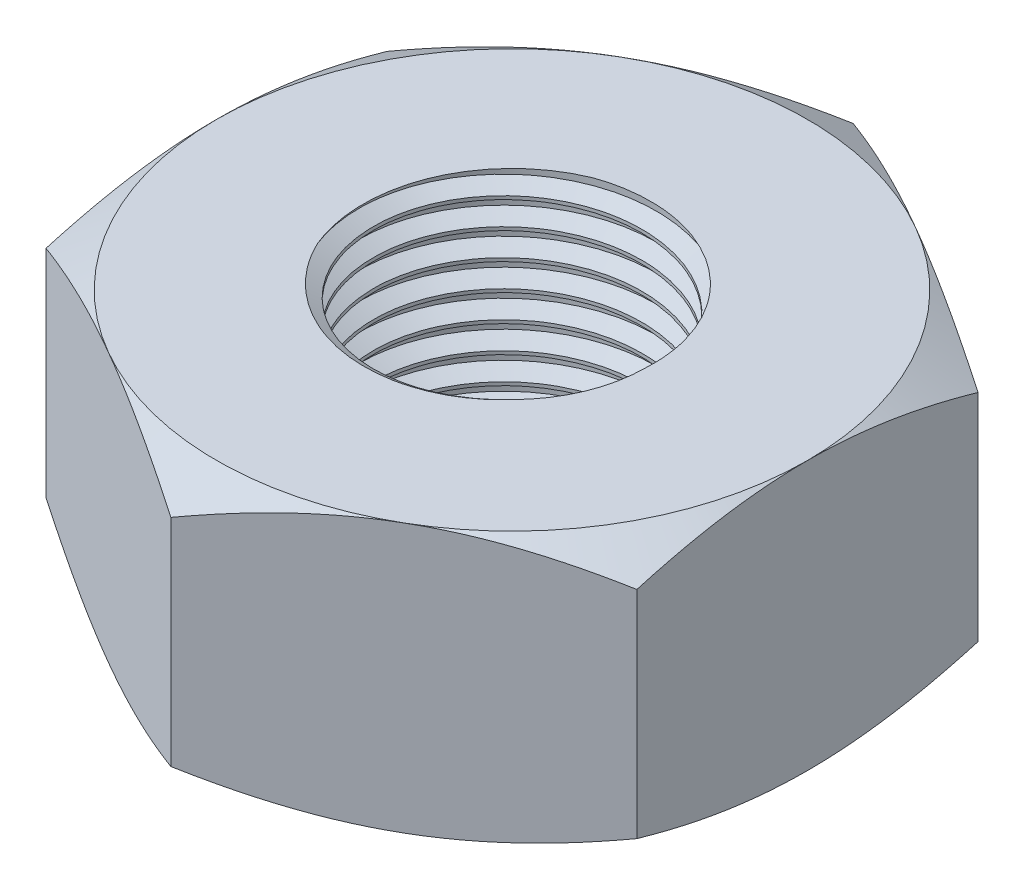
SolidWorks part; units mm, degrees
ref_plane "Front Plane" through (0, 0, 0) normal (0, 0, 1) x (1, 0, 0)
ref_plane "Top Plane" through (0, 0, 0) normal (0, 1, 0) x (1, 0, 0)
ref_plane "Right Plane" through (0, 0, 0) normal (1, 0, 0) x (0, 0, -1)
sketch "Sketch1" plane through (0, 0, 0) normal (0, 1, 0) x (1, 0, 0)
  line L1 (0, 25.4034) -> (-22, 12.7017)
  line L2 (-22, 12.7017) -> (-22, -12.7017)
  line L3 (-22, -12.7017) -> (0, -25.4034)
  line L4 (0, -25.4034) -> (22, -12.7017)
  line L5 (22, -12.7017) -> (22, 12.7017)
  line L6 (22, 12.7017) -> (0, 25.4034)
  circle A0 centre (0, 0) radius 22 construction
  dimension "D1" = 44
extrude "Boss-Extrude1" add sketch "Sketch1" along normal mid plane 20
hole_wizard "M22x2.0 Tapped Hole1" positions "Sketch3" profile "Sketch4" tap size "M22x2.0" standard "ANSI Metric" end condition through all
sketch "Sketch3" plane through (0, 10, 0) normal (0, 1, 0) x (1, 0, 0)
  point P0 (0, 0)
sketch "Sketch4" plane through (0, 10, 0) normal (1, 0, 0) x (0, 0, 1)
  line L0 (0, 0) -> (0, 20)
  line L1 (0, 20) -> (10, 20)
  line L2 (10, 20) -> (10, 0)
  line L5 (10, 0) -> (0, 0)
  line L11 (0, -6.35) -> (0, 107.95) construction
  dimension "Thru Tap Drill Dia." = 20
  dimension "Thru Tap Drill Depth" = 20
cosmetic thread "Hole Thread1" parameters "D2"=22
thread "Thread1" pitch 2 method cut profile "Thread Profile1" start angle 0, offset 5, length 40, pitch 2, diameter 20
ref_plane "Plane1" through (-10, 15, 0) normal (0, 0, -1) x (1, 0, 0)
sketch "Thread Profile1" plane through (-10, 15, 0) normal (0, 0, -1) x (1, 0, 0)
  line L0 (0, 0) -> (0, 2) construction
  line L11 (0, 0) -> (0, 1.75)
  line L12 (0, 1.75) -> (-1.0825, 1.125)
  line L13 (-1.0825, 1.125) -> (-1.0825, 0.625)
  line L15 (-1.0825, 0.625) -> (0, 0)
  line L17 (-1.0825, 0.875) -> (0, 0.875) construction
  point P2 (0, 0)
  dimension "Pitch" = 2
  dimension "Profile_Angle" = 60
  dimension "Profile_Land" = 0.5
  dimension "Profile_Height" = 1.0825
sketch "Sketch7" plane through (0, 10, 0) normal (0, 1, 0) x (1, 0, 0)
  line L0 (-22, 12.7017) -> (-22, -12.7017) construction
  circle A0 centre (0, 0) radius 22
extrude "Cut-Extrude1" cut sketch "Sketch7" against normal through all draft 60 flip side to cut
mirror "Mirror1" about plane through (0, 0, 0) normal (0, 1, 0) of "Cut-Extrude1"
